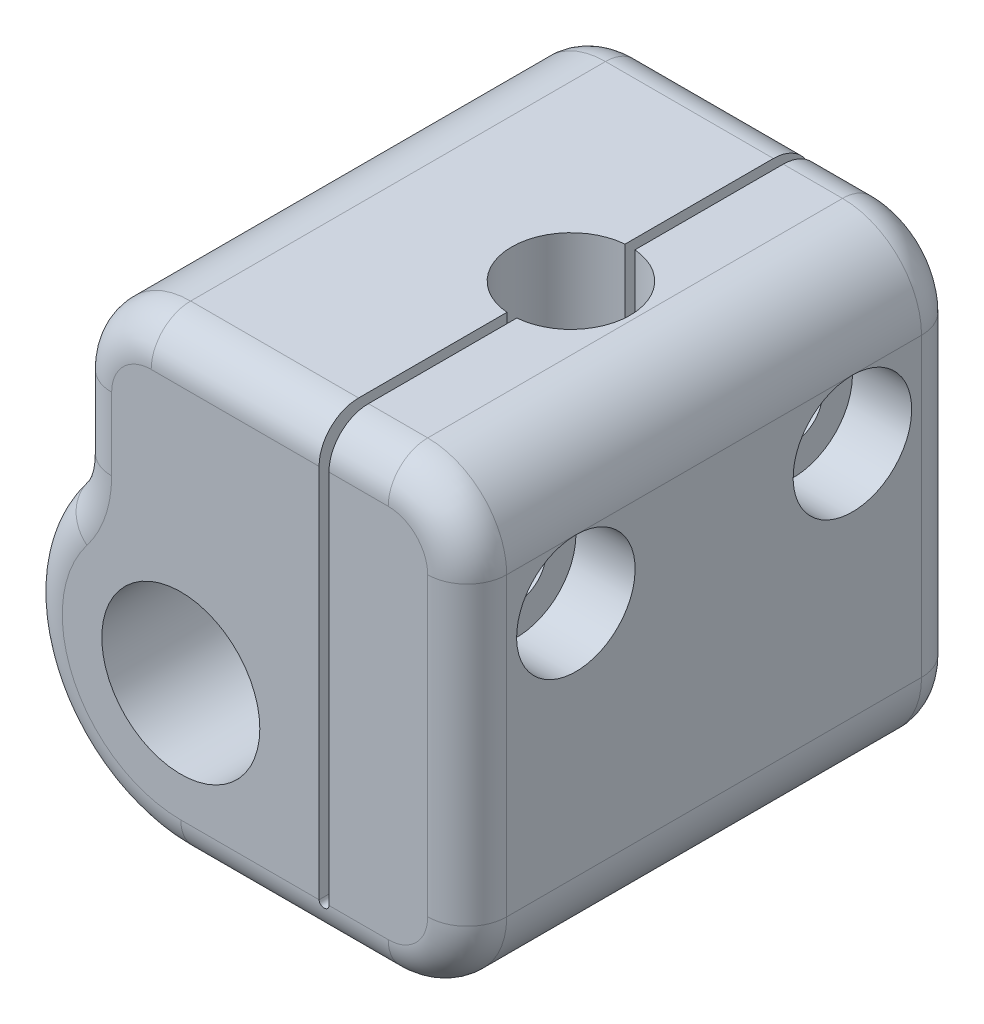
SolidWorks part; units mm, degrees
material "ABS"
ref_plane "Front" through (0, 0, 0) normal (0, 0, 1) x (1, 0, 0)
ref_plane "Top" through (0, 0, 0) normal (0, 1, 0) x (1, 0, 0)
ref_plane "Right" through (0, 0, 0) normal (1, 0, 0) x (0, 0, -1)
sketch "Esquisse1" plane through (0, 0, 0) normal (0, 0, 1) x (1, 0, 0)
  line L0 (0.25, 23) -> (7.25, 23)
  line L1 (-12.75, 23) -> (-0.25, 23)
  line L2 (-12.75, 23) -> (-12.75, 13.8095)
  line L3 (-7.25, 0) -> (7.25, 0)
  line L4 (7.25, 23) -> (7.25, 0)
  line L6 (-0.25, 23) -> (-0.25, 2)
  line L7 (-0.25, 2) -> (0.25, 2) construction
  line L8 (0.25, 23) -> (0.25, 2)
  arc A2 (-0.25, 2) -> (0.25, 2) centre (0, 2) ccw
  circle A3 centre (-7.25, 8) radius 4
  arc A4 (-12.75, 13.8095) -> (-7.25, 0) centre (-7.25, 8) ccw
  dimension "D1" = 7
  dimension "D6" = 8
  dimension "D7" = 16
  dimension "D8" = 4
  dimension "D9" = 7
  dimension "D2" = 20
  dimension "D3" = 23
  dimension "D4" = 0.5
  dimension "D5" = 2
extrude "Boss.-Extru.1" add sketch "Esquisse1" along normal mid plane 25
sketch "Esquisse2" plane through (0, 0, 0) normal (0, 1, 0) x (1, 0, 0)
  circle A0 centre (0, 0) radius 3
  dimension "D1" = 6
extrude "Enlèv. mat.-Extru.1" cut sketch "Esquisse2" along normal through all from offset 4
fillet "Congé3" radius 4 4 edges at (7.25, 0, 0) (-12.75, 13.8095, 0) (-12.75, 23, 0) (7.25, 23, 0)
fillet "Congé4" radius 2 20 edges at (-4.5, 23, -12.5) (-11.5784, 21.8284, -12.5) (-12.75, 17.1657, -12.5) (-12.9641, 14.0404, -12.5) (-14.4299, 4.4716, -12.5) (-2, 0, -12.5) (6.0784, 1.1716, -12.5) (1.75, 23, -12.5) (6.0784, 21.8284, -12.5) (-4.5, 23, 12.5) (-11.5784, 21.8284, 12.5) (-12.75, 17.1657, 12.5) (-12.9641, 14.0404, 12.5) (-14.4299, 4.4716, 12.5) (-2, 0, 12.5) (6.0784, 1.1716, 12.5) (1.75, 23, 12.5) (6.0784, 21.8284, 12.5) (7.25, 11.5, -12.5) (7.25, 11.5, 12.5)
sketch "Esquisse3" plane through (7.25, 0, 0) normal (1, 0, 0) x (0, 0, -1)
  line L0 (0, 50) -> (0, -50) construction
  circle A0 centre (-7, 16) radius 1.5
  circle A1 centre (7, 16) radius 1.5
  dimension "D1" = 16
  dimension "D2" = 14
  dimension "D3" = 3
extrude "Enlèv. mat.-Extru.2" cut sketch "Esquisse3" against normal through all
sketch "Esquisse4" plane through (7.25, 0, 0) normal (1, 0, 0) x (0, 0, -1)
  circle A0 centre (-7, 16) radius 3
  circle A1 centre (7, 16) radius 3
  dimension "D1" = 6
extrude "Enlèv. mat.-Extru.3" cut sketch "Esquisse4" against normal blind 3
sketch "Esquisse5" plane through (-12.75, 0, 0) normal (-1, 0, 0) x (0, 0, 1)
  line L1 (-3.8246, 16) -> (-5.4123, 18.75)
  line L2 (-5.4123, 18.75) -> (-8.5877, 18.75)
  line L3 (-8.5877, 18.75) -> (-10.1754, 16)
  line L4 (-10.1754, 16) -> (-8.5877, 13.25)
  line L5 (-8.5877, 13.25) -> (-5.4123, 13.25)
  line L6 (-5.4123, 13.25) -> (-3.8246, 16)
  line L7 (5.4123, 18.75) -> (3.8246, 16)
  line L8 (3.8246, 16) -> (5.4123, 13.25)
  line L9 (5.4123, 13.25) -> (8.5877, 13.25)
  line L10 (8.5877, 13.25) -> (10.1754, 16)
  line L11 (10.1754, 16) -> (8.5877, 18.75)
  line L12 (8.5877, 18.75) -> (5.4123, 18.75)
  circle A0 centre (-7, 16) radius 2.75 construction
  circle A1 centre (7, 16) radius 2.75 construction
  dimension "D1" = 5.5
extrude "Enlèv. mat.-Extru.4" cut sketch "Esquisse5" against normal blind 3 and the other way blind 3
sketch "Esquisse6" plane through (0, 0, 12.5) normal (0, 0, 1) x (1, 0, 0)
  circle A0 centre (-3.2203, 11.3624) radius 22.5573
extrude "Boss.-Extru.2" [suppressed] add sketch "Esquisse6" against normal blind 0.2
